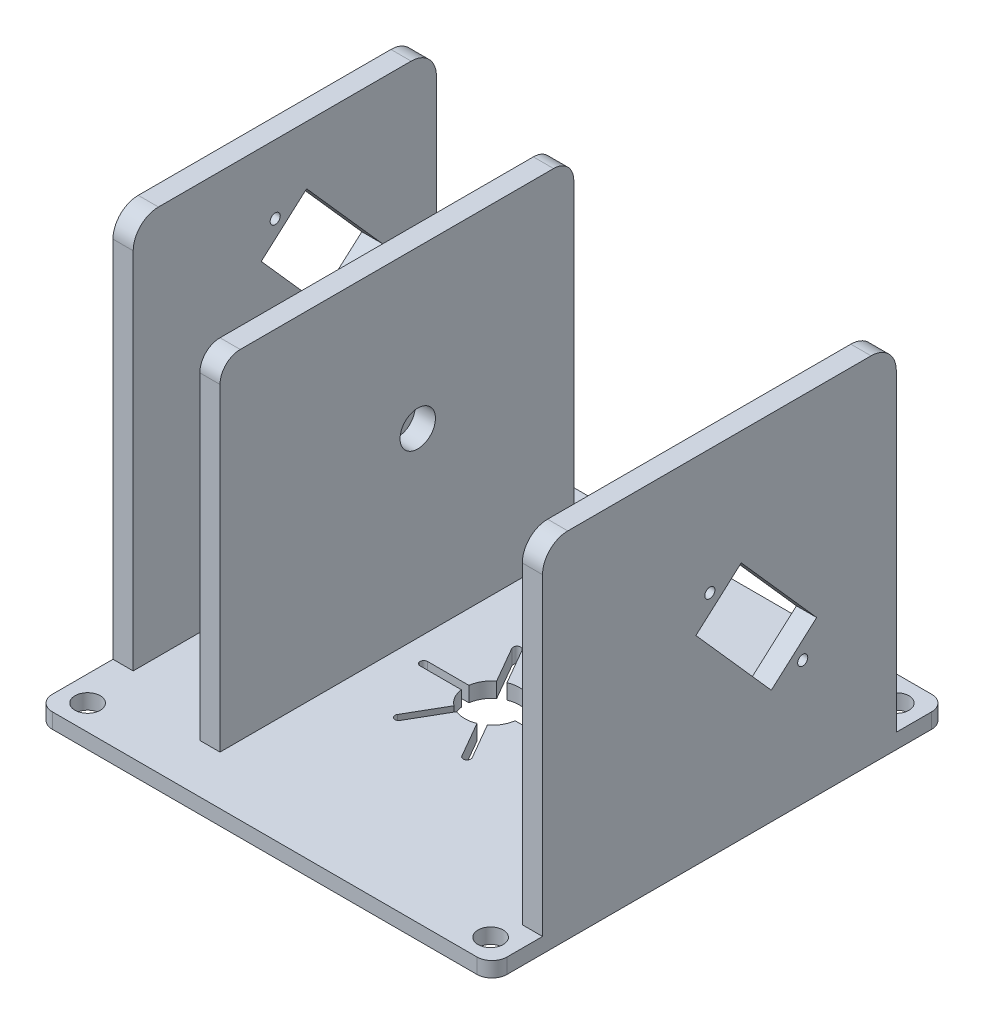
SolidWorks part; units mm, degrees
ref_plane "Front Plane" through (0, 0, 0) normal (0, 0, 1) x (1, 0, 0)
ref_plane "Top Plane" through (0, 0, 0) normal (0, 1, 0) x (1, 0, 0)
ref_plane "Right Plane" through (0, 0, 0) normal (1, 0, 0) x (0, 0, -1)
sketch "Sketch1" plane through (0, 0, 0) normal (0, 1, 0) x (1, 0, 0)
  line L0 (-50.7713, 34.2125) -> (-46.7713, 34.2125)
  line L1 (-50.7713, -40.7875) -> (39.2287, -40.7875)
  line L2 (-50.7713, -40.7875) -> (-50.7713, 49.2125)
  line L3 (-50.7713, 49.2125) -> (39.2287, 49.2125)
  line L4 (39.2287, -40.7875) -> (39.2287, 49.2125)
  line L5 (39.2287, 39.2125) -> (39.2287, -30.7875)
  line L6 (-24.2713, -31.1062) -> (-28.2713, -31.1062)
  line L7 (-46.7713, 34.2125) -> (-46.7713, -25.7875)
  line L8 (-46.7713, -25.7875) -> (-50.7713, -25.7875)
  line L9 (39.2287, 39.2125) -> (35.2287, 39.2125)
  line L10 (35.2287, 39.2125) -> (35.2287, -30.7875)
  line L11 (35.2287, -30.7875) -> (39.2287, -30.7875)
  line L12 (-24.2713, -31.1062) -> (-24.2713, 38.8938)
  line L13 (-24.2713, 38.8938) -> (-28.2713, 38.8938)
  line L14 (-28.2713, -31.1062) -> (-28.2713, 38.8938)
  line L17 (-50.7713, 34.2125) -> (-50.7713, -25.7875)
  point P0 (0, 0)
  point P13 (3.7124, 4.3448)
  dimension "D1" = 90
  dimension "D2" = 90
  dimension "D3" = 15
  dimension "D4" = 15
  dimension "D5" = 4
  dimension "D6" = 4
  dimension "D7" = 18.5
  dimension "D8" = 4
  dimension "D9" = 70
  dimension "D11" = 10
  dimension "D12" = 10
  dimension "D13" = 70
extrude "Boss-Extrude1" add sketch "Sketch1" along normal blind 3 contours L11 L10 L9 L4 L3 L2 L0 L7 L8 L1 L6 L14 L13 L12 | L10 L11 L4 L9 | L8 L7 L0 L2 | L14 L6 L12 L13 region at (-5.2206, 0, -4.2248) region at (-48.7713, 0, -4.2125) region at (37.2287, 0, -4.2125) region at (-26.2713, 0, -3.8938)
extrude "Boss-Extrude2" add sketch "Sketch1<3>" along normal blind 70 contours L8 L7 L0 L2 | L10 L11 L5 L9 region at (-48.7713, 0, -4.2125)
sketch "Sketch1<3>" plane through (0, 0, 0) normal (0, 1, 0) x (1, 0, 0) same geometry as "Sketch1"
extrude "Boss-Extrude3" add sketch "Sketch1<4>" along normal blind 70 contours L14 L13 L12 L6
sketch "Sketch1<4>" plane through (0, 0, 0) normal (0, 1, 0) x (1, 0, 0) same geometry as "Sketch1"
sketch "Sketch5" plane through (-50.7713, 0, 0) normal (-1, 0, 0) x (0, 0, 1)
  line L0 (-8.0225, 70) -> (-8.0225, 0) construction
  line L5 (-34.2125, 70) -> (-34.2125, 3) construction
  circle A0 centre (-8.0225, 60) radius 4
  dimension "D1" = 60
  dimension "D3" = 8
  dimension "D2" = 26.19
extrude "Cut-Extrude4" cut sketch "Sketch5" against normal blind 10
sketch "Sketch6" plane through (0, 3, 0) normal (0, 1, 0) x (1, 0, 0)
  line L0 (-50.7876, 44.2125) -> (49.2124, 44.2125) construction
  line L3 (-50.7876, -35.7875) -> (49.2124, -35.7875) construction
  line L8 (-50.7713, -40.7875) -> (39.2287, -40.7875) construction
  line L9 (-50.7713, 49.2125) -> (39.2287, 49.2125) construction
  circle A0 centre (-45.7876, -35.7875) radius 2.5
  circle A1 centre (-45.7876, 44.2125) radius 2.5
  circle A2 centre (43.7185, 44.2125) radius 2.5
  circle A3 centre (43.7185, -35.7875) radius 2.5
  dimension "D1" = 5
  dimension "D2" = 5
  dimension "D3" = 5
  dimension "D4" = 5
extrude "Cut-Extrude5" cut sketch "Sketch6" against normal blind 10
extrude "Boss-Extrude4" add sketch "Sketch1<5>" along normal blind 80 contours L7 L8 L17 L0
sketch "Sketch1<5>" plane through (0, 0, 0) normal (0, 1, 0) x (1, 0, 0) same geometry as "Sketch1"
extrude "Cut-Extrude6" cut sketch "Sketch5<2>" against normal blind 10
sketch "Sketch5<2>" plane through (-50.7713, 0, 0) normal (-1, 0, 0) x (0, 0, 1) same geometry as "Sketch5"
fillet "Fillet1" radius 3 4 edges at (-50.7713, 1.5, -49.2125) (-50.7713, 1.5, 40.7875) (39.2287, 1.5, -49.2125) (39.2287, 1.5, 40.7875)
fillet "Fillet2" radius 5 4 edges at (-48.7713, 80, -34.2125) (37.2287, 70, -39.2125) (37.2287, 70, 30.7875) (-48.7713, 80, 25.7875)
fillet "Fillet3" radius 4 2 edges at (-26.2713, 70, -38.8938) (-26.2713, 70, 31.1062)
sketch "Sketch7" plane through (39.2287, 0, 0) normal (1, 0, 0) x (0, 0, -1)
  line L0 (-30.7875, -10) -> (39.2125, -10) construction
  line L1 (-30.7875, 65) -> (-30.7875, 3) construction
  line L2 (39.2125, 65) -> (39.2125, 3) construction
  line L3 (-37.7875, 0) -> (46.2125, 0) construction
  circle A0 centre (27.4823, -10) radius 2.5
  dimension "D1" = 10
extrude "Cut-Extrude7" cut sketch "Sketch7" against normal blind 10 rebuild error yes
sketch "Sketch8" plane through (39.2287, 0, 0) normal (1, 0, 0) x (0, 0, -1)
  line L0 (39.2125, 20) -> (-30.7875, 20) construction
  line L1 (39.2125, 65) -> (39.2125, 3) construction
  line L2 (-30.7875, 65) -> (-30.7875, 3) construction
  line L3 (26.9146, 20) -> (8.0207, 38.8939) construction
  circle A0 centre (8.0207, 38.8939) radius 2.5
  dimension "D3" = 5
  dimension "D1" = 26.72
  dimension "D2" = 45
extrude "Cut-Extrude8" cut sketch "Sketch8" against normal blind 10
sketch "Sketch9" plane through (39.2287, 0, 0) normal (1, 0, 0) x (0, 0, -1)
  circle A0 centre (8.0207, 38.8939) radius 3.5
  dimension "D1" = 7
extrude "Cut-Extrude9" cut sketch "Sketch9" against normal up to surface (67.5 mm away) up to face at (-28.2713, 46.6095, -3.8938)
sketch "Sketch26" plane through (0, 3, 0) normal (0, 1, 0) x (1, 0, 0)
  line L0 (39.2287, 39.2125) -> (39.2287, 46.2125) construction
  line L1 (39.2287, -37.7875) -> (39.2287, -30.7875) construction
  circle A0 centre (34.2287, 44.2125) radius 2.5
  circle A2 centre (34.2287, -36.0634) radius 2.5
  dimension "D1" = 5
  dimension "D2" = 5
  dimension "D3" = 5
  dimension "D4" = 5
extrude "Cut-Extrude11" cut sketch "Sketch26" against normal blind 10 contours A2 | A0 region at (34.2287, 3, 36.0634)
sketch "Sketch27" plane through (0, 3, 0) normal (0, 1, 0) x (1, 0, 0)
  line L0 (-49.8926, 48.3339) -> (38.35, -39.9088) construction
  line L1 (38.35, 48.3339) -> (-49.8926, -39.9088) construction
  line L2 (7.7287, 4.2125) -> (-19.2713, 4.2125) construction
  line L3 (7.7287, 3.4625) -> (-19.2713, 3.4625)
  line L4 (7.7287, 4.9625) -> (-19.2713, 4.9625)
  line L5 (0.9787, -7.4788) -> (-12.5213, 15.9039) construction
  line L6 (0.3292, -7.8538) -> (-13.1708, 15.5289)
  line L7 (1.6282, -7.1038) -> (-11.8718, 16.2789)
  line L8 (-12.5213, -7.4788) -> (0.9787, 15.9039) construction
  line L9 (-13.1708, -7.1038) -> (0.3292, 16.2789)
  line L10 (-11.8718, -7.8538) -> (1.6282, 15.5289)
  line L11 (-19.2713, 4.2125) -> (7.7287, 4.2125) construction
  line L12 (-19.2713, 4.9625) -> (7.7287, 4.9625)
  line L13 (-19.2713, 3.4625) -> (7.7287, 3.4625)
  line L14 (-12.5213, 15.9039) -> (0.9787, -7.4788) construction
  line L15 (-11.8718, 16.2789) -> (1.6282, -7.1038)
  line L16 (-13.1708, 15.5289) -> (0.3292, -7.8538)
  line L17 (0.9787, 15.9039) -> (-12.5213, -7.4788) construction
  line L18 (1.6282, 15.5289) -> (-11.8718, -7.8538)
  line L19 (0.3292, 16.2789) -> (-13.1708, -7.1038)
  arc A0 (-47.7713, 49.2125) -> (-50.7713, 46.2125) centre (-47.7713, 46.2125) ccw construction
  arc A1 (36.2287, -40.7875) -> (39.2287, -37.7875) centre (36.2287, -37.7875) ccw construction
  arc A2 (39.2287, 46.2125) -> (36.2287, 49.2125) centre (36.2287, 46.2125) ccw construction
  arc A3 (-50.7713, -37.7875) -> (-47.7713, -40.7875) centre (-47.7713, -37.7875) ccw construction
  arc A4 (7.7287, 3.4625) -> (7.7287, 4.9625) centre (7.7287, 4.2125) ccw
  arc A5 (-19.2713, 4.9625) -> (-19.2713, 3.4625) centre (-19.2713, 4.2125) ccw
  circle A9 centre (-5.7713, 4.2125) radius 5.375
  arc A10 (0.3292, -7.8538) -> (1.6282, -7.1038) centre (0.9787, -7.4788) ccw
  arc A11 (-11.8718, 16.2789) -> (-13.1708, 15.5289) centre (-12.5213, 15.9039) ccw
  arc A12 (-13.1708, -7.1038) -> (-11.8718, -7.8538) centre (-12.5213, -7.4788) ccw
  arc A13 (1.6282, 15.5289) -> (0.3292, 16.2789) centre (0.9787, 15.9039) ccw
  arc A14 (-19.2713, 4.9625) -> (-19.2713, 3.4625) centre (-19.2713, 4.2125) ccw
  arc A15 (7.7287, 3.4625) -> (7.7287, 4.9625) centre (7.7287, 4.2125) ccw
  arc A16 (-11.8718, 16.2789) -> (-13.1708, 15.5289) centre (-12.5213, 15.9039) ccw
  arc A17 (0.3292, -7.8538) -> (1.6282, -7.1038) centre (0.9787, -7.4788) ccw
  arc A18 (1.6282, 15.5289) -> (0.3292, 16.2789) centre (0.9787, 15.9039) ccw
  arc A19 (-13.1708, -7.1038) -> (-11.8718, -7.8538) centre (-12.5213, -7.4788) ccw
  circle A20 centre (-5.7713, 4.2125) radius 2.75
  point P18 (-5.7713, 4.2125)
  point P30 (-5.7713, 4.2125)
  point P37 (-5.7713, 4.2125)
  point P44 (-5.7713, 4.2125)
  point P51 (-5.7713, 4.2125)
  point P58 (-5.7713, 4.2125)
  point P63 (-5.7713, 4.2125)
  dimension "D1" = 10.75
  dimension "D2" = 0.75
  dimension "D3" = 13.5
  dimension "D4" = 6
extrude "Cut-Extrude14" cut sketch "Sketch27" against normal blind 10 contours L3 A5 L4 A4 | L6 A11 L7 A10 | L10 A13 L9 A12
extrude "Cut-Extrude15" cut sketch "Sketch27<7>" against normal blind 10 contours L3 A20 L9 | L6 A20 L4 | L9 A20 L7 | L4 A20 L10 | L7 A20 L3 | L10 A20 L6 region at (-3.7669, 3, -3.0553) region at (-3.7669, 3, -5.3698) region at (-5.7713, 3, -1.898) region at (-5.7713, 3, -6.5271) region at (-7.7757, 3, -3.0553) region at (-7.7757, 3, -5.3698)
sketch "Sketch27<7>" plane through (0, 3, 0) normal (0, 1, 0) x (1, 0, 0) same geometry as "Sketch27"
sketch "Sketch28" plane through (-50.7713, 0, 0) normal (-1, 0, 0) x (0, 0, 1)
  line L0 (-23.4588, 51.635) -> (-8.5312, 68.47)
  line L1 (-8.5312, 68.47) -> (0.4475, 60.5086)
  line L2 (0.4475, 60.5086) -> (-14.4801, 43.6736)
  line L3 (-14.4801, 43.6736) -> (-23.4588, 51.635)
  line L4 (-8.0225, 60) -> (-12.6884, 54.7379) construction
  line L5 (-12.6884, 54.7379) -> (-25.2505, 40.5707) construction
  line L6 (-8.0225, 60) -> (2.1094, 71.4266) construction
  circle A0 centre (-8.0225, 60) radius 4 construction
  circle A1 centre (-8.0225, 60) radius 4
  circle A2 centre (-2.3169, 66.4347) radius 1
  circle A3 centre (-20.6944, 45.709) radius 1
  point P8 (-18.9694, 47.6543)
  dimension "D3" = 2
  dimension "D4" = 8.6
  dimension "D5" = 27.7
  dimension "D1" = 22.5
  dimension "D2" = 12
  dimension "D6" = 2.6
extrude "Cut-Extrude16" cut sketch "Sketch28" against normal up to surface (4 mm away) up to face at (-46.7713, 60, -12.0225)
sketch "Sketch29" plane through (39.2287, 0, 0) normal (1, 0, 0) x (0, 0, -1)
  line L8 (8.0207, 38.8939) -> (0.0593, 47.8726) construction
  line L9 (0.0593, 47.8726) -> (37.8759, 5.2239) construction
  line L10 (8.5294, 47.3639) -> (23.457, 30.5289)
  line L11 (23.457, 30.5289) -> (14.4783, 22.5675)
  line L12 (14.4783, 22.5675) -> (-0.4493, 39.4025)
  line L13 (-0.4493, 39.4025) -> (8.5294, 47.3639)
  circle A6 centre (8.0207, 38.8939) radius 3.5 construction
  circle A7 centre (8.0207, 38.8939) radius 3.5
  circle A8 centre (2.3151, 45.3286) radius 1
  circle A9 centre (20.6926, 24.6028) radius 1
  point P4 (4.04, 43.3832)
  point P28 (18.9676, 26.5482)
  dimension "D4" = 2.6
  dimension "D5" = 27.7
  dimension "D6" = 2
  dimension "D7" = 2
  dimension "D2" = 12
  dimension "D3" = 22.5
  dimension "D8" = 8.6
extrude "Cut-Extrude18" cut sketch "Sketch29" against normal up to surface (4 mm away) up to face at (35.2287, 38.8939, -11.5207)
sketch "Sketch31" plane through (0, 3, 0) normal (0, 1, 0) x (1, 0, 0)
  circle A0 centre (-5.7713, 4.2125) radius 5.375
  dimension "D1" = 10.75
extrude "Cut-Extrude19" cut sketch "Sketch31" against normal blind 10
